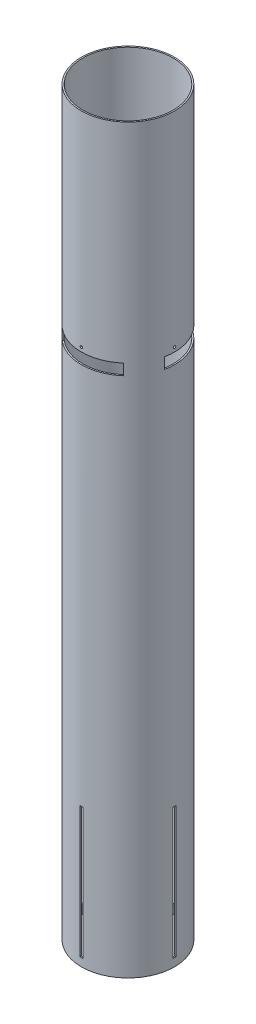
SolidWorks part; units mm, degrees
material "A-Glass Fiber"
ref_plane "Front Plane" through (0, 0, 0) normal (0, 0, 1) x (1, 0, 0)
ref_plane "Top Plane" through (0, 0, 0) normal (0, 1, 0) x (1, 0, 0)
ref_plane "Right Plane" through (0, 0, 0) normal (1, 0, 0) x (0, 0, -1)
sketch "Sketch1" plane through (0, 0, 0) normal (0, 1, 0) x (1, 0, 0)
  circle A0 centre (0, 0) radius 49.53
  circle A1 centre (0, 0) radius 51.1048
  dimension "D1" = 99.06
  dimension "D2" = 102.2096
extrude "Boss-Extrude1" add sketch "Sketch1" along normal blind 812.8
ref_plane "Plane1" through (0, 0, 0) normal (0.7071, 0, 0.7071) x (0.7071, 0, -0.7071)
ref_axis "Axis1" through (0, 812.8, 0) along (0, -1, 0)
sketch "Sketch2" plane through (0, 0, 0) normal (1, 0, 0) x (0, 0, -1)
  line L0 (0, 0) -> (0, 8.89)
  line L1 (1.5875, 8.89) -> (-1.5875, 8.89)
  line L2 (1.5875, 8.89) -> (1.5875, 152.4)
  line L3 (1.5875, 152.4) -> (-1.5875, 152.4)
  line L4 (-1.5875, 8.89) -> (-1.5875, 152.4)
  line L5 (1.5875, 8.89) -> (-1.5875, 152.4) construction
  line L6 (1.5875, 152.4) -> (-1.5875, 8.89) construction
  line L7 (51.1048, 812.8) -> (-51.1048, 812.8) construction
  line L8 (51.1048, 812.8) -> (-51.1048, 812.8)
  line L9 (0, 812.8) -> (0, 588.645)
  line L10 (-51.1048, 0) -> (51.1048, 0) construction
  circle A0 centre (0, 588.645) radius 1.3525
  point P0 (0, 80.645)
  dimension "D4" = 2.7051
  dimension "D1" = 3.175
  dimension "D5" = 588.645
  dimension "D3" = 152.4
  dimension "D2" = 8.89
extrude "Cut-Extrude1" cut sketch "Sketch2" against normal through all contours L4 L1 L2 L3 region at (0, 80.645, 0)
pattern_circular "CirPattern1" count 4 over 360 about axis through (0, 0, 0) along (0, 1, 0) of "Cut-Extrude1" reverse direction yes
extrude "Cut-Extrude2" cut sketch "Sketch2<3>" against normal through all contours A0 region at (0, 587.7157, 0.9293)
sketch "Sketch2<3>" plane through (0, 0, 0) normal (1, 0, 0) x (0, 0, -1) same geometry as "Sketch2"
pattern_circular "CirPattern2" count 4 over 360 about axis through (0, 812.8, 0) along (0, -1, 0) of "Cut-Extrude2"
sketch "Sketch3" plane through (0, 0, 0) normal (0.7071, 0, 0.7071) x (0.7071, 0, -0.7071)
  line L0 (0, 0) -> (0, 127) construction
  circle A0 centre (0, 127) radius 3.175
  dimension "D1" = 6.35
  dimension "D2" = 127
extrude "Cut-Extrude3" cut sketch "Sketch3" against normal through all
ref_plane "Plane3" through (0, 583.8825, 0) normal (0, 1, 0) x (1, 0, 0)
sketch "Sketch7" plane through (0, 583.8825, 0) normal (0, 1, 0) x (1, 0, 0)
  line L0 (0, 0) -> (-50.1228, -9.9701)
  line L1 (0, 0) -> (0, 93.232) construction
  line L2 (0, 0) -> (-16.4271, 48.3927)
  line L3 (-51.1048, 0) -> (0, 0) construction
  arc A0 (-51.0869, 1.3526) -> (-51.0869, -1.3525) centre (0, 0) ccw construction
  circle A1 centre (0, 0) radius 49.53 construction
  circle A2 centre (0, 0) radius 51.1048
  circle A3 centre (0, 0) radius 51.1048
  circle A4 centre (0, 0) radius 49.53
  circle A5 centre (0, 0) radius 51.1048 construction
  arc A6 (1.3526, 51.0869) -> (-1.3525, 51.0869) centre (0, 0) ccw construction
  arc A7 (-51.0869, 1.3526) -> (-51.0869, -1.3525) centre (0, 0) ccw
  arc A8 (1.3526, 51.0869) -> (-1.3525, 51.0869) centre (0, 0) ccw
  dimension "D1" = 82.5
  dimension "D3" = 11.25
  dimension "D2" = 0
extrude "Cut-Extrude4" cut sketch "Sketch7" against normal blind 12.065 contours A4 A3 L0 region at (-49.4835, 583.8825, 9.1481)
pattern_circular "CirPattern3" count 3 over 360 about axis through (0, 812.8, 0) along (0, -1, 0) of "Cut-Extrude4"
equation "\"D1@Boss-Extrude1\" = \"Aft_Section_Length\""
equation "\"AB_Coupler_OD_Length\"= 1in"
equation "\"AB_Coupling_Section_Length\"= 0.375in"
equation "\"AB_Coupler_Length\"= \"AB_Coupler_OD_Length\" + \"AB_Coupling_Section_Length\" * 2"
equation "\"AB_Coupler_Num_Screws\"= 4"
equation "\"AB_Coupling_Screw_Diameter\"= 0.1065in"
equation "\"Aft_Section_Length\" = 32in"
equation "\"D4@Sketch2\"=\"AB_Coupling_Screw_Diameter\""
equation "\"D1@CirPattern2\"=\"AB_Coupler_Num_Screws\""
equation "\"Rail_Nut_From_Bottom\"= 5in"
equation "\"Rail_Nut_Diam\"= 0.25in"
equation "\"D1@Sketch3\"=\"Rail_Nut_Diam\""
equation "\"D2@Sketch3\"=\"Rail_Nut_From_Bottom\""
equation "\"AB_BKHD_Thickness\"= 0.375in"
equation "\"AB_Mount_From_Bottom\"= 23.175in"
equation "\"Cutout_Angle\" = 60"
equation "\"Motor_OD\" = 54mm"
equation "\"Motor_Length\" = 401mm"
equation "\"Mid_Coupler_Length\" = 12in"
equation "\"AB_Paddle_Height\" = 0.375in"
equation "\"Num_Cutouts\" = 4"
equation "\"AB_Coupler_OD\"= 4.024in"
equation "\"AB_Coupler_ID\"= 3.7in"
equation "\"AB_Coupler_Surface_Diameter\"= 3.899in"
equation "\"AB_Central_Bushing_Length\" = 0.75in"
equation "\"Lead_Screw_Dist\" = 2in"
equation "\"Lead_Screw_Diam\" = 0.375in"
equation "\"Lead_Screw_Length\" = \"Mid_Coupler_Length\" + 2*0.375in + 2*0.5in"
equation "\"Paddle_Pin_Offset\" = 0.25in"
equation "\"Paddle_Pin_Radius\" = 2.25*2/3in"
equation "\"Paddle_Gear_OD\" = 3.2in"
equation "\"Fwd_BKHD_From_Top\" = 18in"
equation "\"Body_Tube_OD\"= 4.024in"
equation "\"Body_Tube_ID\"= 3.90in"
equation "\"Coupler_OD\" = 3.899in"
equation "\"Coupler_ID\" = 3.755in"
equation "\"Fwd_Section_Length\" = 20in"
equation "\"Mid_Section_Length\" = 4in"
equation "\"Aft_Upper_Tube_Length\" = 10in"
equation "\"Aft_Lower_Tube_Length\" = 18in"
equation "\"Nosecone_Coupler_Length\" = 5in"
equation "\"Avionics_Bulkhead_Thickness\" = 0.25in"
equation "\"Avionics_Bulkhead_Lip\" = 0.125in"
equation "\"Avionics_Board_Length\" = \"Mid_Coupler_Length\" - 2*\"Avionics_Bulkhead_Lip\""
equation "\"Lead_Screw_Hole_Diam\" = 0.386in"
equation "\"Centering_Ring_Cutout_Dia\"=1.5in"
equation "\"D2@Sketch1\"=\"Body_Tube_OD\""
equation "\"D1@Sketch1\"=\"Body_Tube_ID\""
